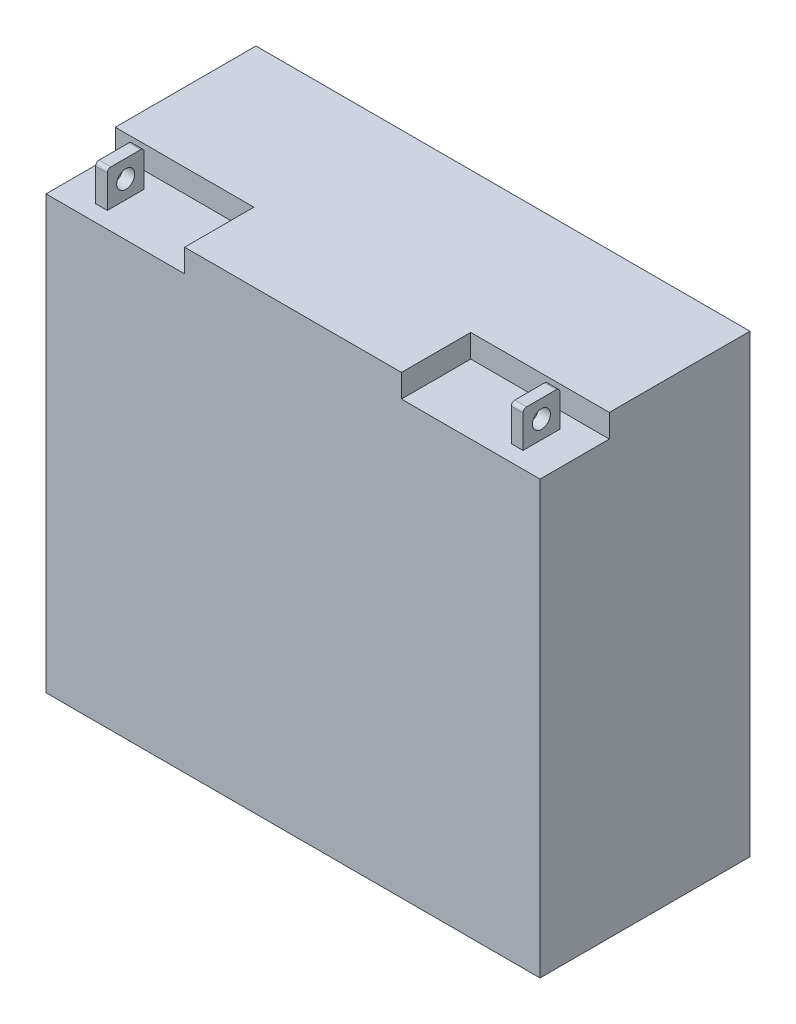
SolidWorks part; units mm, degrees
ref_plane "Front Plane" through (0, 0, 0) normal (0, 0, 1) x (1, 0, 0)
ref_plane "Top Plane" through (0, 0, 0) normal (0, 1, 0) x (1, 0, 0)
ref_plane "Right Plane" through (0, 0, 0) normal (1, 0, 0) x (0, 0, -1)
sketch "Sketch2" plane through (0, 0, 0) normal (0, 1, 0) x (1, 0, 0)
  line L1 (-90.551, -38.481) -> (90.551, -38.481)
  line L2 (-90.551, -38.481) -> (-90.551, 38.481)
  line L3 (-90.551, 38.481) -> (90.551, 38.481)
  line L4 (90.551, -38.481) -> (90.551, 38.481)
  line L5 (-90.551, -38.481) -> (90.551, 38.481) construction
  line L6 (-90.551, 38.481) -> (90.551, -38.481) construction
  point P0 (0, 0)
  dimension "D1" = 181.102
  dimension "D2" = 76.962
extrude "Boss-Extrude1" add sketch "Sketch2" along normal blind 166.878
sketch "Sketch3" plane through (0, 166.878, 0) normal (0, 1, 0) x (1, 0, 0)
  line L0 (-88.7322, 0) -> (89.8475, 0) construction
  text T0 "Top" font "Century Gothic" height in points 36
wrap "Wrap1" [suppressed] sketch "Sketch3" source sketch "Sketch3" thickness 3.81 parameters "D1"=3.81
sketch "Sketch4" plane through (0, 166.878, 0) normal (0, 1, 0) x (1, 0, 0)
  line L0 (0, 0) -> (0, -38.481)
  line L1 (-90.551, -38.481) -> (90.551, -38.481) construction
  line L2 (0, 0) -> (0, 38.481)
  line L3 (90.551, 38.481) -> (-90.551, 38.481) construction
  line L4 (90.551, -13.081) -> (39.751, -13.081)
  line L5 (39.751, -13.081) -> (39.751, -38.481)
  line L8 (90.551, -38.481) -> (90.551, 38.481)
  line L9 (90.551, 38.481) -> (-90.551, 38.481)
  line L10 (-90.551, 38.481) -> (-90.551, -38.481)
  line L11 (-90.551, -38.481) -> (90.551, -38.481)
  line L12 (90.551, -38.481) -> (90.551, 38.481)
  line L13 (90.551, 38.481) -> (-90.551, 38.481)
  line L14 (-90.551, 38.481) -> (-90.551, -38.481)
  line L15 (-90.551, -38.481) -> (90.551, -38.481)
  line M7 (90.551, -38.481) -> (90.551, 38.481)
  line M8 (90.551, 38.481) -> (-90.551, 38.481)
  line M9 (-90.551, 38.481) -> (-90.551, -38.481)
  line M10 (-90.551, -38.481) -> (90.551, -38.481)
  dimension "D2" = 25.4
  dimension "D3" = 50.8
  dimension "D1" = 0
extrude "Cut-Extrude1" cut sketch "Sketch4" against normal through all contours L0 L2 M8 M9 M10 region at (-45.2755, 166.878, 0)
extrude "Cut-Extrude2" cut sketch "Sketch4<3>" against normal blind 8.4667 contours L4 L5 M10 M7 region at (65.151, 166.878, 25.781)
sketch "Sketch4<3>" plane through (0, 166.878, 0) normal (0, 1, 0) x (1, 0, 0) same geometry as "Sketch4"
sketch "Sketch5" plane through (0, 158.4113, 0) normal (0, 1, 0) x (1, 0, 0)
  line L0 (0, 38.481) -> (0, -38.481) construction
  line L1 (78.359, -32.512) -> (74.041, -32.512)
  line L2 (78.359, -32.512) -> (78.359, -19.05)
  line L3 (78.359, -19.05) -> (74.041, -19.05)
  line L4 (90.551, -13.081) -> (39.751, -13.081)
  line L5 (39.751, -13.081) -> (39.751, -38.481)
  line L6 (39.751, -38.481) -> (90.551, -38.481)
  line L7 (90.551, -38.481) -> (90.551, -13.081)
  line L8 (90.551, -13.081) -> (39.751, -13.081)
  line L9 (39.751, -13.081) -> (39.751, -38.481)
  line L10 (39.751, -38.481) -> (90.551, -38.481)
  line L11 (90.551, -38.481) -> (90.551, -13.081)
  line L12 (74.041, -32.512) -> (74.041, -19.05)
  line L13 (78.359, -32.512) -> (74.041, -19.05) construction
  line L14 (78.359, -19.05) -> (74.041, -32.512) construction
  line L15 (76.2, -25.781) -> (90.551, -25.781) construction
  point P2 (76.2, -25.781)
  dimension "D2" = 76.2
  dimension "D3" = 13.462
  dimension "D4" = 4.318
  dimension "D1" = 0
extrude "Boss-Extrude2" add sketch "Sketch5" along normal blind 13.208 contours L12 L1 L2 L3 region at (76.2, 158.4113, 25.781)
sketch "Sketch6" plane through (78.359, 0, 0) normal (1, 0, 0) x (0, 0, -1)
  line L1 (-32.512, 158.4113) -> (-25.781, 158.4113)
  line L2 (-32.512, 158.4113) -> (-32.512, 165.0153)
  line L3 (-32.512, 165.0153) -> (-25.781, 165.0153) construction
  line L4 (-32.512, 158.4113) -> (-19.05, 158.4113)
  line L5 (-19.05, 158.4113) -> (-19.05, 171.6193)
  line L6 (-19.05, 171.6193) -> (-32.512, 171.6193)
  line L7 (-32.512, 171.6193) -> (-32.512, 158.4113)
  line L8 (-32.512, 158.4113) -> (-19.05, 158.4113)
  line L9 (-19.05, 158.4113) -> (-19.05, 171.6193)
  line L10 (-19.05, 171.6193) -> (-32.512, 171.6193)
  line L11 (-32.512, 171.6193) -> (-32.512, 158.4113)
  line L12 (-25.781, 158.4113) -> (-25.781, 165.0153) construction
  line L13 (-32.512, 171.6193) -> (-32.512, 158.4113) construction
  circle A0 centre (-25.781, 165.0153) radius 3.302
  point P6 (-25.781, 158.4113)
  point P10 (-32.512, 165.0153)
  dimension "D2" = 6.604
  dimension "D1" = 0
extrude "Cut-Extrude3" cut sketch "Sketch6" against normal blind 13.208 contours A0 region at (78.359, 165.0153, 25.781)
fillet "Fillet1" radius 1.27 2 edges at (76.2, 171.6193, 19.05) (76.2, 171.6193, 32.512)
mirror "Mirror1" about plane through (0, 0, 0) normal (-1, 0, 0) of bodies 105
